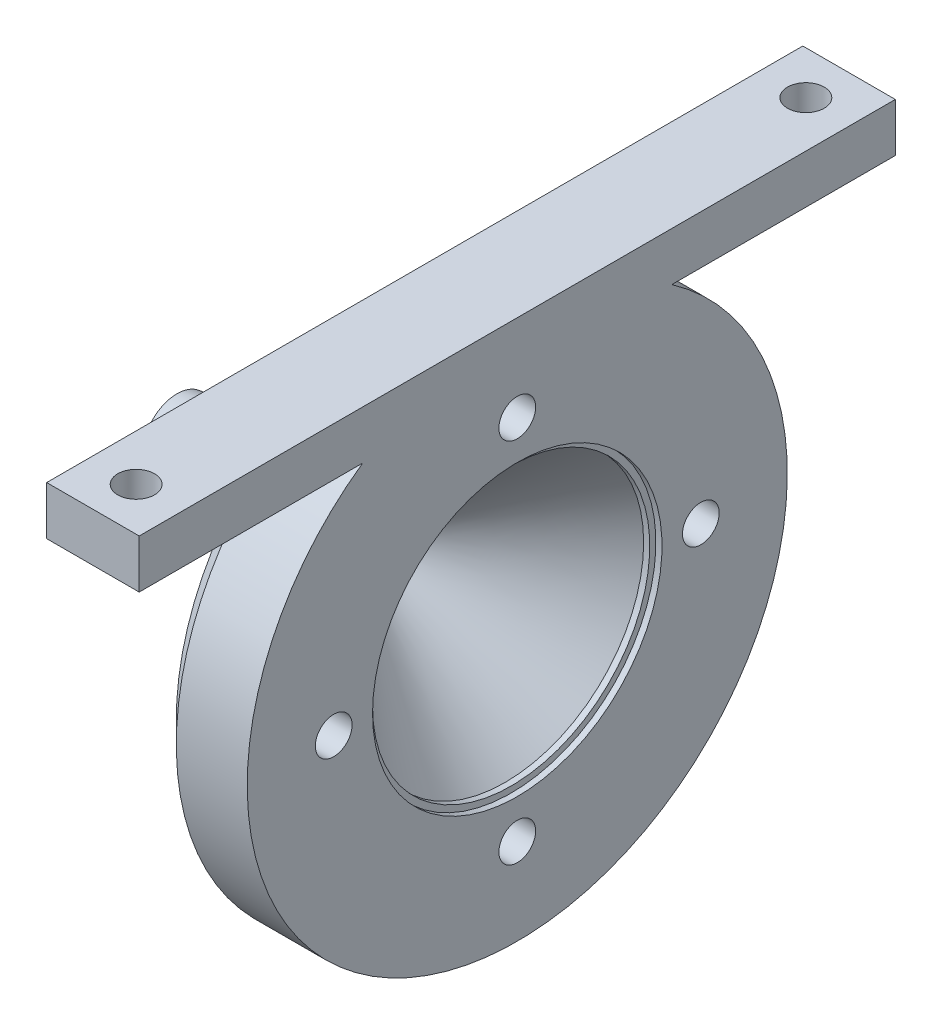
SolidWorks part; units mm, degrees
ref_plane "Front Plane" through (0, 0, 0) normal (0, 0, 1) x (1, 0, 0)
ref_plane "Top Plane" through (0, 0, 0) normal (0, 1, 0) x (1, 0, 0)
ref_plane "Right Plane" through (0, 0, 0) normal (1, 0, 0) x (0, 0, -1)
sketch "Sketch1" plane through (0, 0, 0) normal (0, 0, 1) x (1, 0, 0)
  line L0 (-801.9206, 0) -> (36107.5283, 0) construction
  line L3 (-14.0102, 3.8) -> (-14.0102, 3.15)
  line L8 (-18.3435, 1.9) -> (0, 1.9)
  line L9 (-18.3435, 1.9) -> (-18.3435, 3.15)
  line L10 (13.1623, 13.4) -> (13.1623, 25)
  line L12 (13.1623, 25) -> (4.5963, 25)
  line L16 (13.1623, 13.4) -> (12.5963, 13.4)
  line L17 (12.5963, 13.4) -> (12.5963, 12.834)
  line L18 (4.5963, 25) -> (4.5963, 12.834)
  line L20 (0, 1.9) -> (12.0303, 12.834)
  line L21 (-18.3435, 3.15) -> (-14.0102, 3.8)
  line L22 (12.0303, 12.834) -> (12.5963, 12.834)
  line L23 (-14.0102, 3.15) -> (-9.6768, 3.8)
  line L25 (-9.6768, 3.15) -> (-5.3435, 3.8)
  line L26 (-9.6768, 3.8) -> (-9.6768, 3.15)
  line L27 (-5.3435, 3.8) -> (4.5963, 12.834)
  line L28 (4.5963, 20.5) -> (13.1623, 20.5)
  dimension "D3" = 0.566
  dimension "D2" = 7.6
  dimension "D6" = 3.8
  dimension "D7" = 6.3
  dimension "D5" = 25
  dimension "D8" = 13.4
  dimension "D10" = 0.566
  dimension "D4" = 5
  dimension "D9" = 0.566
  dimension "D11" = 13
  dimension "D12" = 8.566
  dimension "D13" = 4.5
revolve "Revolve17" add sketch "Sketch1" angle 360 about L0
sketch "Sketch4" plane through (4.5963, 0, 0) normal (-1, 0, 0) x (0, 0, 1)
  circle A0 centre (0, 0) radius 16.9947 construction
  point P3 (0, 16.9947)
  point P7 (16.9947, 0)
  point P12 (-16.9947, 0)
  point P13 (0, -16.9947)
hole_wizard "M3 Clearance Hole1" positions "Sketch4" profile "Sketch5" hole size "M3" standard "ISO"
sketch "Sketch5" plane through (4.5963, -16.9947, 0) normal (0, 1, 0) x (0, 0, 1)
  line L0 (0, 0) -> (0, 9.5875)
  line L1 (0, 9.5875) -> (1.7, 8.566)
  line L2 (1.7, 8.566) -> (1.7, 0)
  line L5 (1.7, 0) -> (0, 0)
  line L10 (0, 9.5875) -> (-1.7, 8.566) construction
  line L11 (0, -6.35) -> (0, 107.95) construction
  dimension "Hole Dia." = 3.4
  dimension "Hole Depth" = 8.566
  dimension "Drill Angle" = 118
chamfer "Chamfer1" distance 2 angle 45 1 edges at (4.5963, 0, 25)
extrude "Boss-Extrude1" add sketch "Sketch1<11>" against normal mid plane 70 contours L18 L28 L10 L12 region at (8.8793, 22.75, 0)
sketch "Sketch1<11>" plane through (0, 0, 0) normal (0, 0, 1) x (1, 0, 0) same geometry as "Sketch1"
sketch "Sketch9" plane through (0, 20.5, 0) normal (0, -1, 0) x (-1, 0, 0)
  line L0 (-4.5963, -35) -> (-13.1623, 35) construction
  line L1 (-4.5963, -10.4283) -> (-4.5963, -35) construction
  line L2 (-4.5963, -35) -> (-13.1623, -35) construction
  line L3 (-13.1623, 35) -> (-13.1623, 14.3091) construction
  line L4 (-13.1623, 35) -> (-4.5963, 35) construction
  line L5 (-4.5963, 35) -> (-13.1623, 35) construction
  line L6 (-4.5963, 35) -> (-13.1623, -35) construction
  line L7 (-13.1623, -14.3091) -> (-13.1623, -35) construction
  line L8 (-8.8793, -35) -> (-8.8793, 35) construction
  line L9 (-4.5963, 0) -> (-13.1623, 0) construction
  line L10 (-13.1623, 25) -> (-13.1623, -25) construction
  circle A0 centre (-8.8793, -31) radius 1.7
  circle A1 centre (-8.8793, 31) radius 1.7
  dimension "D1" = 3.4
  dimension "D2" = 4
extrude "Cut-Extrude1" cut sketch "Sketch9" against normal blind 10
equation "\"D10@Sketch1\"=\"D3@Sketch1\""
equation "\"D9@Sketch1\"=\"D3@Sketch1\""
